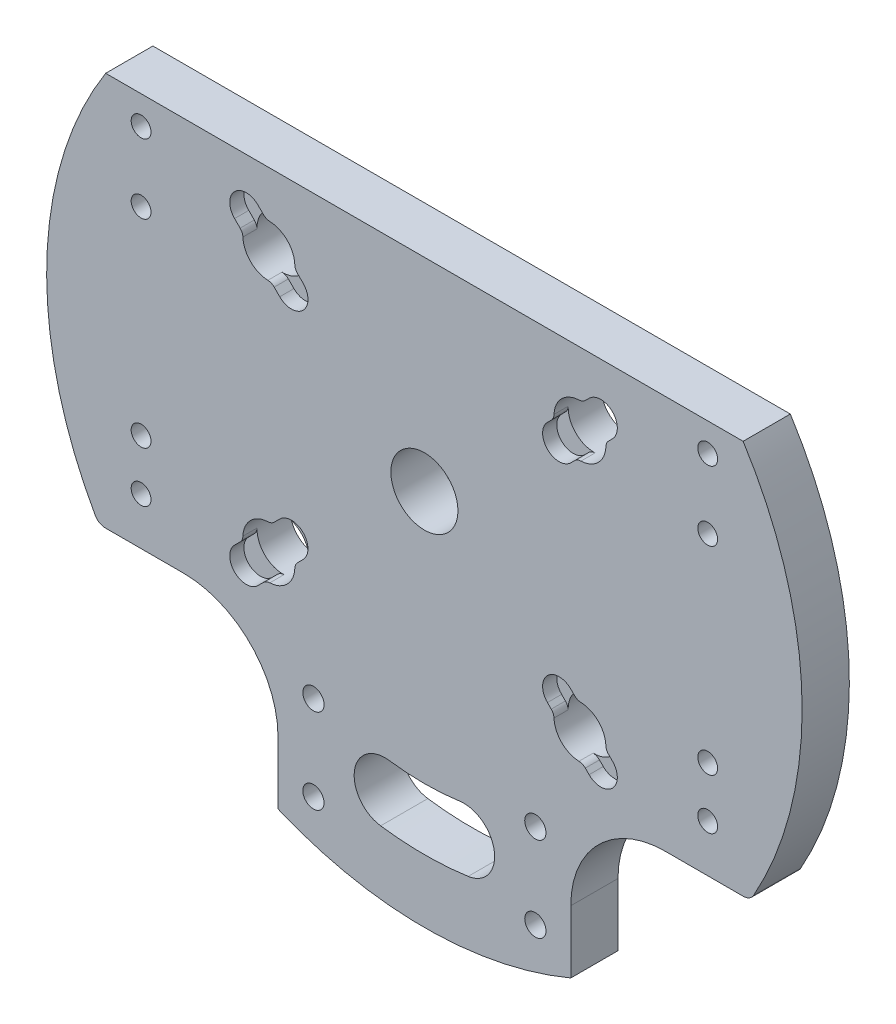
SolidWorks part; units mm, degrees
ref_plane "Front Plane" through (0, 0, 0) normal (0, 0, 1) x (1, 0, 0)
ref_plane "Top Plane" through (0, 0, 0) normal (0, 1, 0) x (1, 0, 0)
ref_plane "Right Plane" through (0, 0, 0) normal (1, 0, 0) x (0, 0, -1)
other "Configuration Table"
sketch "草图5" plane through (0, 0, 0) normal (0, 0, 1) x (1, 0, 0)
  line L0 (0, 0) -> (0, 43.4) construction
  line L1 (-67.5, 42.9389) -> (67.5, 42.9389)
  arc A0 (-67.5, 42.9389) -> (67.5, 42.9389) centre (0, 0) ccw
extrude "凸台-拉伸2" add sketch "草图5" along normal blind 10
sketch "草图6" plane through (0, 0, 0) normal (0, 0, -1) x (-1, 0, 0)
  line L0 (0, 0) -> (0, 62) construction
  line L1 (0, 0) -> (-51.9615, -30) construction
  line L2 (0, 0) -> (-80, 0) construction
  circle A0 centre (0, 0) radius 80 construction
  circle A1 centre (-51.9615, 30) radius 2.5
  circle A2 centre (-51.9615, -30) radius 2.5
  circle A3 centre (51.9615, -30) radius 2.5
  circle A4 centre (51.9615, 30) radius 2.5
  point P13 (0, 0)
  dimension "D2" = 2
  dimension "D1" = 60
extrude "切除-拉伸1" cut sketch "草图6" against normal blind 8
sketch "草图7" plane through (0, 0, 0) normal (0, 0, -1) x (-1, 0, 0)
  circle A0 centre (32.9399, -27.6399) radius 5.5
  circle A1 centre (32.9399, 27.6399) radius 5.5
  circle A2 centre (-32.9465, 27.632) radius 5.5
  circle A3 centre (-32.9465, -27.632) radius 5.5
extrude "切除-拉伸2" cut sketch "草图7" against normal through all
sketch "草图8" plane through (0, 0, 10) normal (0, 0, 1) x (1, 0, 0)
  line L0 (0, 0) -> (0, -56.1) construction
  line L1 (0, 0) -> (-9.2723, -65.9759) construction
  line L2 (0, 0) -> (9.2723, -65.9759) construction
  arc A0 (-9.2723, -65.9759) -> (9.2723, -65.9759) centre (0, 0) ccw
  arc A1 (-7.4597, -53.0784) -> (7.4597, -53.0784) centre (0, 0) ccw
  arc A2 (-9.2723, -65.9759) -> (-7.4597, -53.0784) centre (-8.366, -59.5271) cw
  arc A3 (9.2723, -65.9759) -> (7.4597, -53.0784) centre (8.366, -59.5271) ccw
  dimension "D1" = 8
  dimension "D2" = 8
extrude "切除-拉伸3" cut sketch "草图8" against normal through all
sketch "草图9" plane through (0, 0, 10) normal (0, 0, 1) x (1, 0, 0)
  line L0 (-32.9399, 27.6399) -> (-32.9399, 22.1399) construction
  line L1 (0, 0) -> (80, 0) construction
  line L2 (-37.721, 32.4209) -> (-28.1588, 22.8588) construction
  line L3 (-35.2461, 34.8958) -> (-25.684, 25.3337)
  line L4 (-40.1959, 29.9461) -> (-30.6337, 20.3839)
  line L5 (32.9465, 27.632) -> (32.9465, 22.132) construction
  line L6 (37.3573, 32.0428) -> (28.5357, 23.2212) construction
  line L7 (39.8322, 29.5679) -> (31.0106, 20.7463)
  line L8 (34.8824, 34.5177) -> (26.0608, 25.6961)
  line L9 (-37.721, -32.4209) -> (-28.1588, -22.8588) construction
  line L10 (-35.2461, -34.8958) -> (-25.684, -25.3337)
  line L11 (-40.1959, -29.9461) -> (-30.6337, -20.3839)
  line L12 (37.3573, -32.0428) -> (28.5357, -23.2212) construction
  line L13 (39.8322, -29.5679) -> (31.0106, -20.7463)
  line L14 (34.8824, -34.5177) -> (26.0608, -25.6961)
  circle A0 centre (-32.9399, 27.6399) radius 5.5 construction
  arc A1 (-67.5, 42.9389) -> (67.5, 42.9389) centre (0, 0) ccw construction
  arc A2 (-35.2461, 34.8958) -> (-40.1959, 29.9461) centre (-37.721, 32.4209) ccw
  arc A3 (-30.6337, 20.3839) -> (-25.684, 25.3337) centre (-28.1588, 22.8588) ccw
  circle A4 centre (32.9465, 27.632) radius 5.5 construction
  arc A5 (39.8322, 29.5679) -> (34.8824, 34.5177) centre (37.3573, 32.0428) ccw
  arc A6 (26.0608, 25.6961) -> (31.0106, 20.7463) centre (28.5357, 23.2212) ccw
  arc A7 (-35.2461, -34.8958) -> (-40.1959, -29.9461) centre (-37.721, -32.4209) cw
  arc A8 (-30.6337, -20.3839) -> (-25.684, -25.3337) centre (-28.1588, -22.8588) cw
  arc A9 (39.8322, -29.5679) -> (34.8824, -34.5177) centre (37.3573, -32.0428) cw
  arc A10 (26.0608, -25.6961) -> (31.0106, -20.7463) centre (28.5357, -23.2212) cw
  point P14 (-32.9399, 27.6399)
  point P26 (32.9465, 27.632)
  point P33 (-32.9399, -27.6399)
  point P40 (32.9465, -27.632)
  dimension "D2" = 45
  dimension "D1" = 45
extrude "切除-拉伸4" cut sketch "草图9" against normal blind 3
fillet "圆角1" radius 2 16 edges at (-33.465, -33.1147, 8.5) (-27.465, -27.1147, 8.5) (-38.4148, -28.165, 8.5) (-32.4148, -22.165, 8.5) (33.4716, -33.1069, 8.5) (27.4716, -27.1069, 8.5) (38.4214, -28.1571, 8.5) (32.4214, -22.1571, 8.5) (27.4716, 27.1069, 8.5) (33.4716, 33.1069, 8.5) (-32.4148, 22.165, 8.5) (-27.465, 27.1147, 8.5) (-38.4148, 28.165, 8.5) (-33.465, 33.1147, 8.5) (32.4214, 22.1571, 8.5) (38.4214, 28.1571, 8.5)
sketch "草图13" plane through (0, 0, 10) normal (0, 0, 1) x (1, 0, 0)
  line L0 (-64.2082, -40.5) -> (-68.9909, -40.5)
  line L2 (-64.2082, -40.5) -> (-31, -40.5)
  line L3 (-31, -40.5) -> (-31, -73.7496)
  line L4 (-31, -73.7496) -> (31, -73.7496)
  line L5 (31, -73.7496) -> (31, -40.5)
  line L6 (31, -40.5) -> (68.9909, -40.5)
  arc A0 (-67.5, 42.9389) -> (67.5, 42.9389) centre (0, 0) ccw construction
  arc A2 (-68.9909, -40.5) -> (68.9909, -40.5) centre (0, 0) ccw
extrude "切除-拉伸7" cut sketch "草图13" against normal through all contours L0 A2 L3 L2 | L5 A2 L6 region at (-44.9947, -52.8, 10) region at (44.9947, -52.8, 10)
sketch "草图16" plane through (0, 0, 0) normal (0, 0, -1) x (-1, 0, 0)
  line L0 (60, 42.9389) -> (60, -40.4611) construction
  line L1 (52.5, 42.9389) -> (67.5, 42.9389) construction
  line L2 (67.5, -40.4611) -> (59.7, -40.4611) construction
  line L4 (52.5, 16.2389) -> (67.5, 16.2389) construction
  line L5 (52.5, -13.7611) -> (67.5, -13.7611) construction
  circle A0 centre (60, 36.9389) radius 3.5
  circle A1 centre (60, 22.2389) radius 3.5
  circle A2 centre (60, -19.7611) radius 3.5
  circle A3 centre (60, -30.4611) radius 3.5
  dimension "D1" = 6
  dimension "D3" = 6
  dimension "D4" = 10
  dimension "D2" = 6
extrude "切除-拉伸8" cut sketch "草图16" against normal blind 3
sketch "草图18" plane through (0, 0, 0) normal (0, 0, -1) x (-1, 0, 0)
  circle A0 centre (60, -30.4611) radius 2.1
  circle A1 centre (60, -19.7611) radius 2.1
  circle A2 centre (60, 22.2389) radius 2.1
  circle A3 centre (60, 36.9389) radius 2.1
extrude "切除-拉伸9" cut sketch "草图18" against normal through all
mirror "镜向1" about plane through (0, 0, 0) normal (1, 0, 0) of "切除-拉伸8", "切除-拉伸9"
fillet "圆角2" radius 20 2 edges at (31, -40.5, 5) (-31, -40.5, 5)
fillet "圆角3" radius 2.5 2 edges at (68.9909, -40.5, 5) (-68.9909, -40.5, 5)
sketch "草图20" plane through (0, 0, 0) normal (0, 0, -1) x (-1, 0, 0)
  line L0 (31, -60.5) -> (31, -73.7496) construction
  circle A0 centre (23.5, -67.7496) radius 3.75
  circle A1 centre (23.5, -49.7496) radius 3.75
  dimension "D1" = 6
  dimension "D2" = 6
  dimension "D3" = 7.5
  dimension "D4" = 7.5
extrude "切除-拉伸11" cut sketch "草图20" against normal blind 3
sketch "草图21" plane through (0, 0, 0) normal (0, 0, -1) x (-1, 0, 0)
  line L0 (31, -60.5) -> (31, -73.7496) construction
  circle A1 centre (23.5, -49.7496) radius 2.25
  circle A2 centre (23.5, -67.7496) radius 2.25
  dimension "D1" = 7.5
  dimension "D2" = 6
  dimension "D3" = 6
  dimension "D4" = 7.5
extrude "切除-拉伸12" cut sketch "草图21" against normal through all
mirror "镜向2" about plane through (0, 0, 0) normal (1, 0, 0) of "切除-拉伸12", "切除-拉伸11"
sketch "草图22" plane through (0, 0, 0) normal (0, 0, -1) x (-1, 0, 0)
  circle A0 centre (0, 0) radius 7.1
  dimension "D1" = 14.2
extrude "切除-拉伸13" cut sketch "草图22" against normal through all
chamfer "倒角1" [suppressed] distance 0.2 angle 45
chamfer "倒角2" [suppressed] distance 0.2 angle 45
